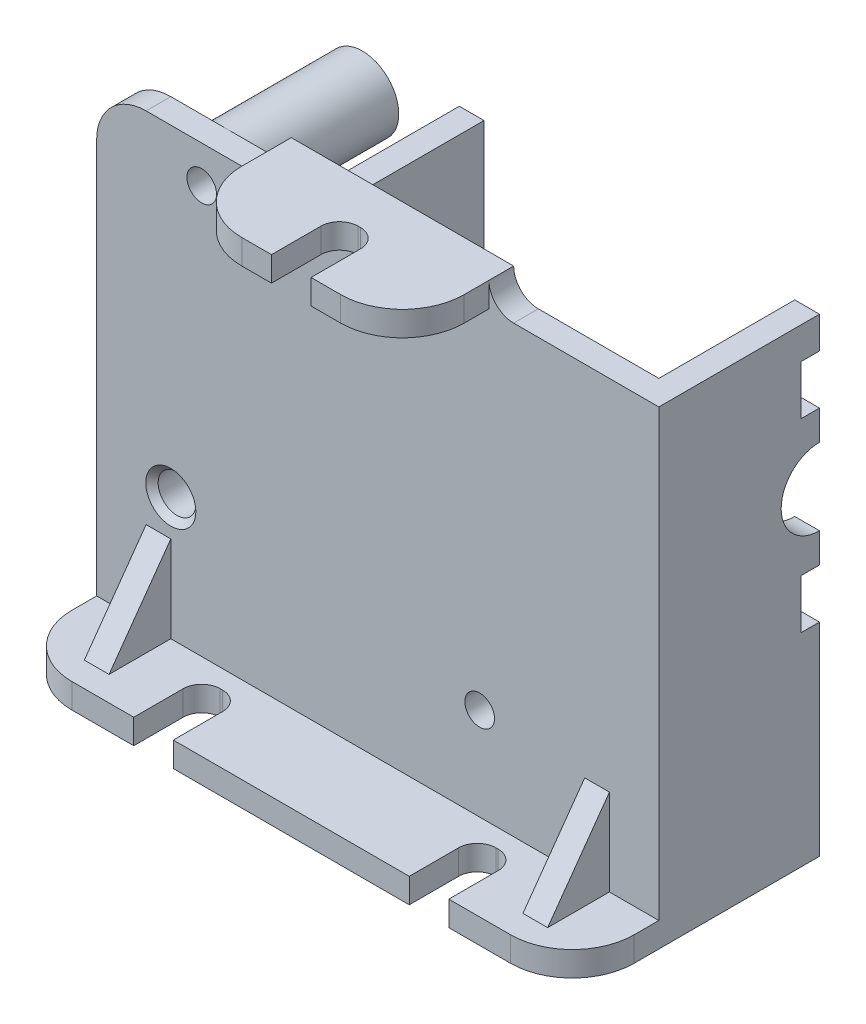
SolidWorks part; units mm, degrees
ref_plane "Face" through (0, 0, 0) normal (0, 0, 1) x (1, 0, 0)
ref_plane "Dessus" through (0, 0, 0) normal (0, 1, 0) x (1, 0, 0)
ref_plane "Droite" through (0, 0, 0) normal (1, 0, 0) x (0, 0, -1)
sketch "Esquisse25" plane through (0, 0, 0) normal (0, 0, 1) x (1, 0, 0)
  point P0 (0, -13.58)
  dimension "D1" = 13.58
ref_axis "Axe1" through (0, -13.58, -50.1087) along (0, 0, 1)
sketch "Esquisse1" plane through (0, 0, 0) normal (0, 0, 1) x (1, 0, 0)
  line L0 (-18.636, 0) -> (40.6725, 0) construction
  line L1 (0, 13.4516) -> (0, -31.9474) construction
  line L2 (-13.58, -13.58) -> (12.9107, -13.58) construction
  line L3 (11, 10.3689) -> (11, -7.2863) construction
  line L4 (12.35, 12.5556) -> (12.35, -11.4741) construction
  line L5 (37.5, 12.5556) -> (37.5, -10.7539) construction
  line L6 (-16.5535, -25.5) -> (42.4584, -25.5) construction
  line L7 (-16.0297, -27.5) -> (41.191, -27.5) construction
  line L8 (-6, 14.3889) -> (-6, -30.5277) construction
  line L9 (12.35, 10.45) -> (38.7737, 10.45) construction
  line L10 (11.7976, -10.45) -> (39.5594, -10.45) construction
  line L11 (39.5, 11.377) -> (39.5, -30.9205) construction
  line L12 (-10.1369, 12.5) -> (39.5, 12.5) construction
  line L14 (-6, 12.5) -> (39.5, 12.5)
  line L15 (-6, 12.5) -> (-6, -25.5)
  line L16 (-6, -25.5) -> (39.5, -25.5)
  line L17 (39.5, 12.5) -> (39.5, -25.5)
  circle A0 centre (0, -13.58) radius 11.5 construction
  circle A1 centre (0, -13.58) radius 1.5
extrude "Base-Extrusion" add sketch "Esquisse1" along normal mid plane 26
sketch "Esquisse5" plane through (0, 12.5, 0) normal (0, 1, 0) x (-1, 0, 0)
  line L0 (-12.35, -16.3279) -> (-12.35, 15.7701) construction
  line L1 (-10.35, -15.9222) -> (-10.35, 14.6545) construction
  line L2 (-37.5, -14.3503) -> (-37.5, 16.7842) construction
  line L3 (-39.5, -13.7925) -> (-39.5, 16.3786) construction
  line L4 (-40.8108, 11) -> (9.1448, 11) construction
  line L5 (-41.2165, -11) -> (8.3249, -11) construction
  line L7 (-37.5, 11) -> (-12.35, 11)
  line L8 (-37.5, 11) -> (-37.5, -11)
  line L9 (-37.5, -11) -> (-12.35, -11)
  line L10 (-12.35, 11) -> (-12.35, -11)
  line L11 (-10.35, 11) -> (8.7031, 11)
  line L12 (-10.35, 11) -> (-10.35, -11)
  line L13 (-10.35, -11) -> (8.7031, -11)
  line L14 (8.7031, 11) -> (8.7031, -11)
extrude "Enlèv. mat.-Extru.6" cut sketch "Esquisse5" against normal blind 40
sketch "Esquisse3" plane through (0, 0, 13) normal (0, 0, 1) x (1, 0, 0)
  circle A0 centre (0, -13.58) radius 3.5
extrude "Boss.-Extru.1" add sketch "Esquisse3" against normal blind 25
sketch "Esquisse4" plane through (0, 0, 13) normal (0, 0, 1) x (1, 0, 0)
  circle A0 centre (0, -13.58) radius 1.525
  dimension "D1" = 13.58
  dimension "D2" = 3.05
extrude "Enlèv. mat.-Extru.2" cut sketch "Esquisse4" against normal through all
sketch "Esquisse6" plane through (39.5, 0, 0) normal (1, 0, 0) x (0, 0, -1)
  line L0 (-13.8762, 0) -> (18.6073, 0) construction
  line L1 (0, 12.5) -> (0, -24.08) construction
  line L2 (-13, 12.5) -> (13, 12.5) construction
  line L3 (11, -13.58) -> (-11, -13.58) construction
  circle A0 centre (0, 0.42) radius 3.025
  dimension "D1" = 6.05
  dimension "D2" = 14
extrude "Enlèv. mat.-Extru.3" cut sketch "Esquisse6" against normal through all
sketch "Esquisse7" plane through (39.5, 0, 0) normal (1, 0, 0) x (0, 0, -1)
  circle A0 centre (0, 0.42) radius 3.1
  circle A1 centre (0, 0.42) radius 3.025 construction
  dimension "D1" = 6.2
extrude "Enlèv. mat.-Extru.4" cut sketch "Esquisse7" against normal blind 3
sketch "Esquisse8" plane through (0, -25.5, 0) normal (0, -1, 0) x (1, 0, 0)
  line L0 (-6, 21.1962) -> (-6, -20.9902) construction
  line L1 (39.5, 20.4108) -> (39.5, -20.9902) construction
  line L2 (41.0671, -20) -> (-8.3785, -20) construction
  line L3 (-7.8207, 20) -> (40.3571, 20) construction
  line L5 (-6, 20) -> (39.5, 20)
  line L6 (-6, 20) -> (-6, 11.9399)
  line L7 (-6, 11.9399) -> (39.5, 11.9399)
  line L8 (39.5, 20) -> (39.5, 11.9399)
  line L9 (-6, -20) -> (39.5, -20)
  line L10 (-6, -20) -> (-6, -11.5095)
  line L11 (-6, -11.5095) -> (39.5, -11.5095)
  line L12 (39.5, -20) -> (39.5, -11.5095)
extrude "Boss.-Extru.2" add sketch "Esquisse8" against normal blind 2
sketch "Esquisse9" plane through (0, 12.5, 0) normal (0, 1, 0) x (-1, 0, 0)
  line L0 (6.6791, -3.1) -> (-6.4741, -3.1) construction
  line L1 (7.282, 3.1) -> (-7.5154, 3.1) construction
  line L3 (6.6791, -3.1) -> (-4.7203, -3.1)
  line L4 (6.6791, -3.1) -> (6.6791, 3.1)
  line L5 (6.6791, 3.1) -> (-4.7203, 3.1)
  line L6 (-4.7203, -3.1) -> (-4.7203, 3.1)
extrude "Enlèv. mat.-Extru.5" cut sketch "Esquisse9" against normal blind 32
sketch "Esquisse12" plane through (0, 0, 0) normal (0, 0, 1) x (1, 0, 0)
  line L0 (-4.6513, 9.5) -> (15.1881, 9.5) construction
  line L1 (18.2023, -16) -> (33.4929, -16) construction
  line L2 (25, -8.6922) -> (25, -25.0789) construction
  line L3 (2.5, 14.9287) -> (2.5, -0.5811) construction
  circle A0 centre (2.5, 9.5) radius 2.95
  circle A1 centre (25, -16) radius 2.95
extrude "Boss.-Extru.3" add sketch "Esquisse12" along normal mid plane 26
sketch "Esquisse13" plane through (0, 0, 0) normal (0, 0, 1) x (1, 0, 0)
  circle A0 centre (2.5, 9.5) radius 1.2
  circle A1 centre (25, -16) radius 1.2
extrude "Enlèv. mat.-Extru.8" cut sketch "Esquisse13" against normal mid plane 32
cosmetic thread "Représentation de filetage1" parameters "D2"=2.9
cosmetic thread "Représentation de filetage2" parameters "D2"=2.9
sketch "Esquisse14" plane through (0, -23.5, 0) normal (0, 1, 0) x (-1, 0, 0)
  line L0 (8.0853, 0) -> (-43.1429, 0) construction
  line L1 (-4, -22.6142) -> (-4, -6.692) construction
  line L2 (-39.5, -22.6142) -> (-39.5, -10.961) construction
  line L3 (-16.75, -22.0374) -> (-16.75, -8.8265) construction
  line L4 (-7.2, -22.0374) -> (-7.2, -8.8265) construction
  line L5 (2.9509, -14.5) -> (-11.9906, -14.5) construction
  line L6 (-26.3, -21.5758) -> (-26.3, -16)
  line L7 (-4, -21.5758) -> (-7.2, -21.5758)
  line L8 (-4, -21.5758) -> (-4, -16)
  line L9 (-5.5, -14.5) -> (-5.7, -14.5)
  line L10 (-7.2, -21.5758) -> (-7.2, -16)
  line L11 (-28, -14.5) -> (-27.8, -14.5)
  line L12 (-29.5, -21.5758) -> (-29.5, -16)
  line L13 (-29.5, -21.5758) -> (-26.3, -21.5758)
  line L14 (-29.5, 21.5758) -> (-26.3, 21.5758)
  line L15 (-29.5, 21.5758) -> (-29.5, 16)
  line L16 (-28, 14.5) -> (-27.8, 14.5)
  line L17 (-7.2, 21.5758) -> (-7.2, 16)
  line L18 (-5.5, 14.5) -> (-5.7, 14.5)
  line L19 (-4, 21.5758) -> (-4, 16)
  line L20 (-4, 21.5758) -> (-7.2, 21.5758)
  line L21 (-26.3, 21.5758) -> (-26.3, 16)
  arc A0 (-5.5, -14.5) -> (-4, -16) centre (-5.5, -16) cw
  arc A1 (-7.2, -16) -> (-5.7, -14.5) centre (-5.7, -16) cw
  arc A2 (-26.3, -16) -> (-27.8, -14.5) centre (-27.8, -16) ccw
  arc A3 (-28, -14.5) -> (-29.5, -16) centre (-28, -16) ccw
  arc A4 (-28, 14.5) -> (-29.5, 16) centre (-28, 16) cw
  arc A5 (-26.3, 16) -> (-27.8, 14.5) centre (-27.8, 16) cw
  arc A6 (-7.2, 16) -> (-5.7, 14.5) centre (-5.7, 16) ccw
  arc A7 (-5.5, 14.5) -> (-4, 16) centre (-5.5, 16) ccw
  dimension "D1" = 1.5
extrude "Enlèv. mat.-Extru.9" cut sketch "Esquisse14" against normal through all
sketch "Esquisse15" plane through (39.5, 0, 0) normal (1, 0, 0) x (0, 0, -1)
  line L0 (-1.5, 9.8002) -> (-1.5, -10.1958) construction
  line L1 (1.5, 9.3323) -> (1.5, -9.7969) construction
  line L2 (-3.0488, 7.5) -> (3.8686, 7.5) construction
  line L3 (-5.6888, 0.42) -> (7.1769, 0.42) construction
  line L4 (-2.4473, 9.92) -> (3.3339, 9.92) construction
  line L5 (-2.4473, 5.92) -> (3.5389, 5.92) construction
  line L6 (-1.5, -5.08) -> (-1.5, -9.08)
  line L7 (1.5, 5.92) -> (-1.5, 5.92)
  line L8 (1.5, 5.92) -> (1.5, 9.92)
  line L9 (1.5, 9.92) -> (-1.5, 9.92)
  line L10 (-1.5, 5.92) -> (-1.5, 9.92)
  line L11 (1.5, -9.08) -> (-1.5, -9.08)
  line L12 (1.5, -5.08) -> (1.5, -9.08)
  line L13 (1.5, -5.08) -> (-1.5, -5.08)
extrude "Enlèv. mat.-Extru.10" cut sketch "Esquisse15" against normal blind 3
fillet "Congé1" radius 5 4 edges at (-6, -24.5, -20) (39.5, -24.5, -20) (-6, -24.5, 20) (39.5, -24.5, 20)
fillet "Congé2" radius 4 1 edges at (-6, 12.5, 12)
chamfer "Chanfrein1" distance 0.5 angle 45 4 edges at (-1.525, -13.58, -3.1) (1.525, -13.58, 3.1) (1.525, -13.58, -13) (1.525, -13.58, 13)
sketch "Esquisse16" plane through (0, 0, 0) normal (0, 0, 1) x (1, 0, 0)
  line L1 (-8.9898, 14.583) -> (40.4766, 14.583)
  line L2 (-8.9898, 14.583) -> (-8.9898, -26.083)
  line L3 (-8.9898, -26.083) -> (40.4766, -26.083)
  line L4 (40.4766, 14.583) -> (40.4766, -26.083)
extrude "Enlèv. mat.-Extru.11" cut sketch "Esquisse16" against normal blind 30
sketch "Esquisse17" plane through (0, 0, 0) normal (0, 0, -1) x (-1, 0, 0)
  line L0 (-24.3953, -13.58) -> (-5.104, -13.58) construction
  line L1 (-14.1468, -6.58) -> (-8.2826, -6.58) construction
  line L2 (-14.4756, -20.58) -> (-7.899, -20.58) construction
  line L4 (-13.7083, -6.58) -> (-8.8855, -6.58)
  line L5 (-13.7083, -6.58) -> (-13.7083, -20.58)
  line L6 (-13.7083, -20.58) -> (-8.8855, -20.58)
  line L7 (-8.8855, -6.58) -> (-8.8855, -20.58)
extrude "Enlèv. mat.-Extru.12" cut sketch "Esquisse17" against normal blind 3
sketch "Esquisse18" plane through (0, -23.5, 0) normal (0, 1, 0) x (-1, 0, 0)
  line L0 (-35.5, 7.0082) -> (-35.5, 24.6038) construction
  line L1 (-33.5, 8.1238) -> (-33.5, 24.0967) construction
  line L2 (2, 9.9493) -> (2, 22.2206) construction
  line L3 (0, 9.9493) -> (0, 22.5755) construction
  line L4 (3.2542, 13) -> (-38.4275, 13) construction
  line L5 (3.7105, 18) -> (-39.9488, 18) construction
  line L7 (-35.5, 18) -> (-33.5, 18)
  line L8 (-35.5, 18) -> (-35.5, 12.6368)
  line L9 (-35.5, 12.6368) -> (-33.5, 12.6368)
  line L10 (-33.5, 18) -> (-33.5, 12.6368)
  line L11 (0, 18) -> (2, 18)
  line L12 (0, 18) -> (0, 12.6368)
  line L13 (0, 12.6368) -> (2, 12.6368)
  line L14 (2, 18) -> (2, 12.6368)
extrude "Boss.-Extru.4" add sketch "Esquisse18" along normal blind 7
chamfer "Chanfrein2" distance 7 distance2 5 2 edges at (-1, -16.5, 18) (34.5, -16.5, 18) first distance on face at (-1, -20, 18) first distance on face at (34.5, -20, 18)
sketch "Esquisse20" plane through (0, 12.5, 0) normal (0, 1, 0) x (-1, 0, 0)
  line L0 (-16.75, 0.5177) -> (-16.75, 30.1787) construction
  line L1 (-31.1212, 20) -> (3.4615, 20) construction
  line L2 (-29.8743, 11) -> (9.2362, 11) construction
  line L3 (-18.35, 12.1983) -> (-18.35, 23.6165) construction
  line L4 (-25.75, 9.6391) -> (-25.75, 28.6038) construction
  line L5 (-28, 14.5) -> (-11.0409, 14.5) construction
  line L6 (-7.75, 11) -> (-25.75, 11)
  line L7 (-25.75, 11) -> (-25.75, 20)
  line L8 (-25.75, 20) -> (-18.35, 20)
  line L9 (-18.35, 20) -> (-18.35, 16)
  line L10 (-16.85, 14.5) -> (-16.65, 14.5)
  line L11 (-15.15, 20) -> (-15.15, 16)
  line L12 (-7.75, 20) -> (-15.15, 20)
  line L13 (-7.75, 11) -> (-7.75, 20)
  arc A0 (-16.85, 14.5) -> (-18.35, 16) centre (-16.85, 16) cw
  arc A1 (-16.65, 14.5) -> (-15.15, 16) centre (-16.65, 16) ccw
  point P23 (-16.75, 14.5)
  point P26 (-16.75, 11)
  dimension "D1" = 1.5
extrude "Boss.-Extru.5" add sketch "Esquisse20" along normal blind 2
fillet "Congé3" radius 2 2 edges at (25.75, 12.5, 12) (7.75, 12.5, 12)
fillet "Congé5" radius 5 2 edges at (25.75, 13.5, 20) (7.75, 13.5, 20)
ref_plane "Plan1" through (0, 0, 0) normal (0, 0, -1) x (-1, 0, 0)
sketch "Esquisse21" plane through (0, 0, 3.1) normal (0, 0, -1) x (-1, 0, 0)
  circle A1 centre (0, -13.58) radius 3.5
  circle A2 centre (0, -13.58) radius 3.5
  dimension "D1" = 0
extrude "Enlèv. mat.-Extru.13" [suppressed] cut sketch "Esquisse21" against normal up to surface (7.9 mm away) up to face at (27.95, -16, 11)
sketch "Esquisse22" plane through (0, 0, 11) normal (0, 0, -1) x (-1, 0, 0)
  circle A0 centre (0, -13.58) radius 3.95
  dimension "D1" = 7.9
extrude "Enlèv. mat.-Extru.14" [suppressed] cut sketch "Esquisse22" against normal blind 1
sketch "Esquisse23" plane through (0, 0, 11) normal (0, 0, -1) x (-1, 0, 0)
  line L0 (6, 8.5) -> (6, -25.5) construction
  circle A0 centre (0, -13.58) radius 5
  circle A1 centre (0, -13.58) radius 6
  dimension "D1" = 10
extrude "Boss.-Extru.6" [suppressed] add sketch "Esquisse23" along normal blind 4
sketch "Esquisse24" [suppressed] plane through (0, 0, 12) normal (0, 0, -1) x (-1, 0, 0)
  circle A0 centre (0, -13.58) radius 2.5
  dimension "D1" = 5
extrude "Enlèv. mat.-Extru.15" [suppressed] cut sketch "Esquisse24" against normal through all
equation "\"D2@Esquisse6\" = 14"
